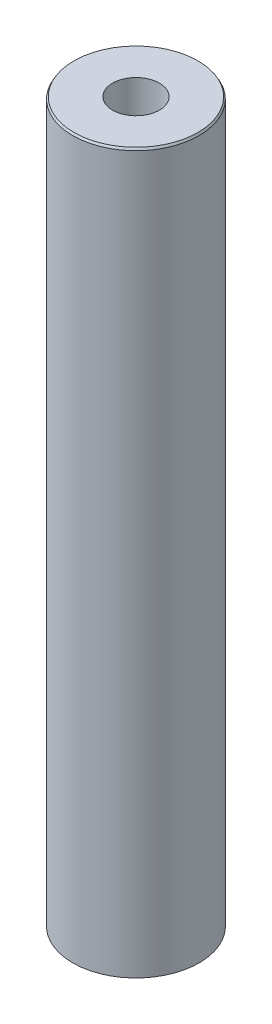
SolidWorks part; units mm, degrees
ref_plane "Front Plane" through (0, 0, 0) normal (0, 0, 1) x (1, 0, 0)
ref_plane "Top Plane" through (0, 0, 0) normal (0, 1, 0) x (1, 0, 0)
ref_plane "Right Plane" through (0, 0, 0) normal (1, 0, 0) x (0, 0, -1)
sketch "Sketch1" plane through (0, 0, 0) normal (0, 1, 0) x (1, 0, 0)
  circle A0 centre (0, 0) radius 50
  dimension "SHAFT_OD" = 100
extrude "Boss-Extrude1" add sketch "Sketch1" along normal blind 568.9199
sketch "Sketch2" plane through (0, 0, 0) normal (0, 1, 0) x (1, 0, 0)
  circle A0 centre (0, 0) radius 18.5218
  dimension "BORE_D" = 37.0436
extrude "Cut-Extrude1" cut sketch "Sketch2" along normal through all
chamfer "Chamfer1" distance 1.6731 angle 30 2 edges at (0, 568.9199, 50) (0, 0, 50) first distance on face at (0, 568.9199, 50) first distance on face at (0, 0, 18.5218)
